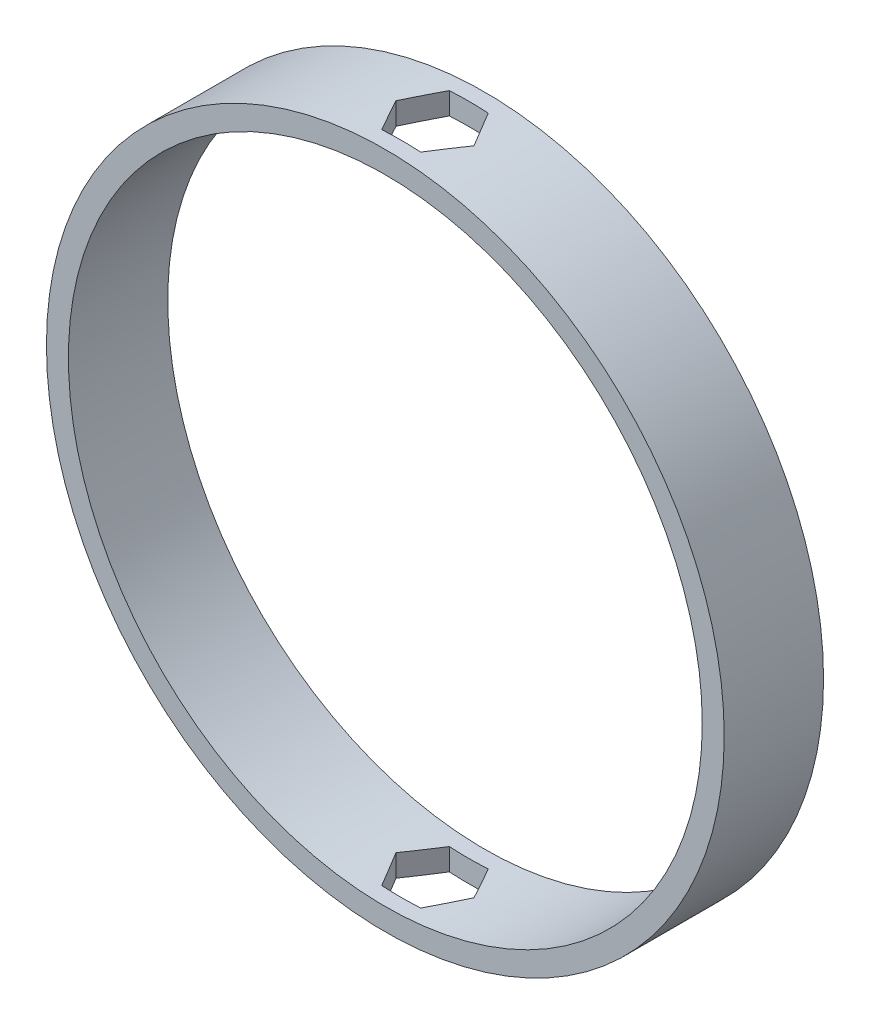
SolidWorks part; units mm, degrees
ref_plane "Front Plane" through (0, 0, 0) normal (0, 0, 1) x (1, 0, 0)
ref_plane "Top Plane" through (0, 0, 0) normal (0, 1, 0) x (1, 0, 0)
ref_plane "Right Plane" through (0, 0, 0) normal (1, 0, 0) x (0, 0, -1)
sketch "Sketch1" plane through (0, 0, 0) normal (0, 0, 1) x (1, 0, 0)
  circle A0 centre (0, 0) radius 34.11
  circle A1 centre (0, 0) radius 31.9
  dimension "D1" = 68.22
  dimension "D2" = 63.8
extrude "Boss-Extrude1" add sketch "Sketch1" along normal blind 10
ref_plane "Plane1" through (0, 34.11, 0) normal (0, 1, 0) x (1, 0, 0)
sketch "Sketch2" plane through (0, 34.11, 0) normal (0, 1, 0) x (1, 0, 0)
  line L0 (0, -5) -> (-3.926, -5) construction
  line L1 (3.926, -5) -> (1.963, -1.6)
  line L2 (1.963, -1.6) -> (-1.963, -1.6)
  line L3 (-1.963, -1.6) -> (-3.926, -5)
  line L4 (-3.926, -5) -> (-1.963, -8.4)
  line L5 (-1.963, -8.4) -> (1.963, -8.4)
  line L6 (1.963, -8.4) -> (3.926, -5)
  circle A1 centre (0, -5) radius 3.4 construction
  dimension "D2" = 5
  dimension "D3" = 6.8
extrude "Cut-Extrude1" cut sketch "Sketch2" against normal through all
